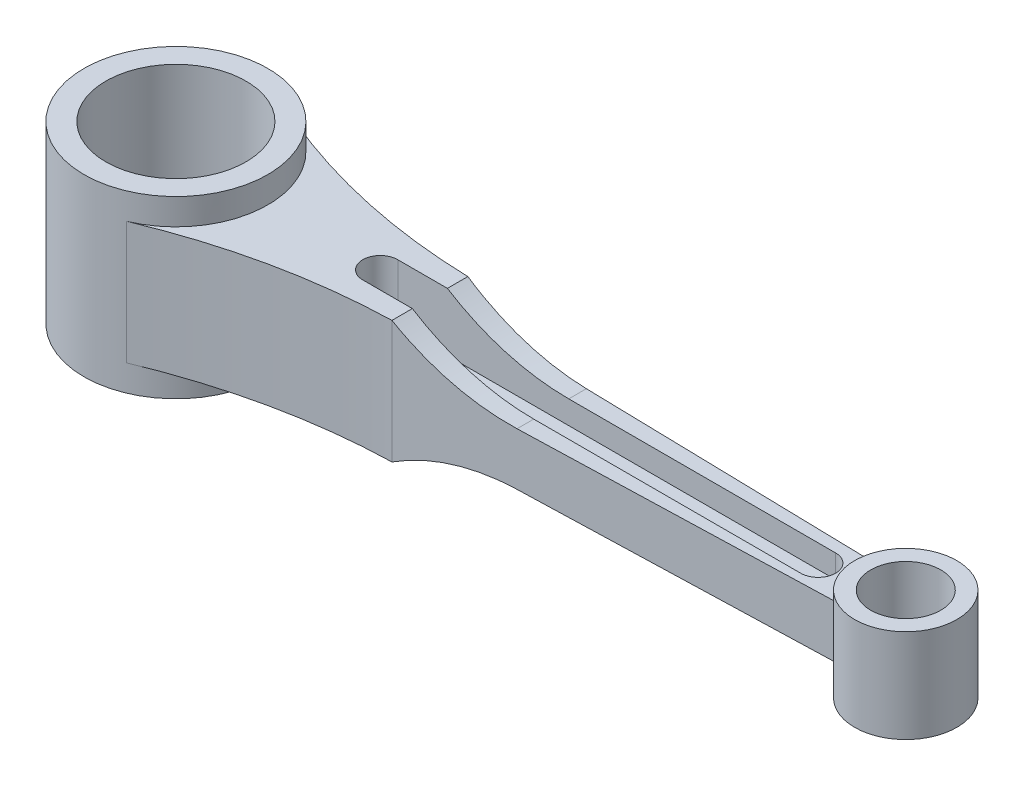
SolidWorks part; units mm, degrees
ref_plane "Front Plane" through (0, 0, 0) normal (0, 0, 1) x (1, 0, 0)
ref_plane "Top Plane" through (0, 0, 0) normal (0, 1, 0) x (1, 0, 0)
ref_plane "Right Plane" through (0, 0, 0) normal (1, 0, 0) x (0, 0, -1)
sketch "Sketch1" plane through (0, 0, 0) normal (0, 1, 0) x (1, 0, 0)
  line L0 (0, 0) -> (150, 0) construction
  line L1 (0, 6) -> (150, 6)
  line L2 (0, -6) -> (150, -6)
  line L3 (17, 13) -> (165.3326, 9.5455)
  line L4 (17, 13) -> (17, -13)
  line L5 (17, -13) -> (164.6777, -8.4545)
  line L6 (17, 13) -> (17, -13) construction
  line L7 (-26.4314, 0) -> (-19.2398, 0) construction
  circle A0 centre (-70, 0) radius 24
  circle A1 centre (-70, 0) radius 31.5
  arc A2 (0, 6) -> (0, -6) centre (0, 0) ccw
  arc A3 (150, -6) -> (150, 6) centre (150, 0) ccw
  circle A4 centre (180, 0) radius 12
  circle A5 centre (180, 0) radius 17.5
  arc A6 (-57.8377, 29.0573) -> (17, 13) centre (22.472, 220.928) ccw
  arc A7 (-57.8377, -29.0573) -> (17, -13) centre (22.472, -220.928) cw
  point P6 (75, 0)
  point P17 (17, 0)
  point P22 (17, 0)
  point P28 (0, 0)
  point P29 (0, 0)
  point P30 (0, 0)
  dimension "D4" = 12
  dimension "D5" = 24
  dimension "D6" = 35
  dimension "D7" = 48
  dimension "D8" = 63
  dimension "D9" = 163
  dimension "D1" = 150
  dimension "D2" = 30
  dimension "D3" = 250
  dimension "D11" = 18
  dimension "D12" = 26
extrude "Boss-Extrude1" add sketch "Sketch1" against normal mid plane 60 contours A1 A0 region at (-44.518, 0, -16.9583)
extrude "Boss-Extrude2" add sketch "Sketch1<4>" against normal mid plane 32 separate body contours A5 A4 region at (184.8376, 0, -16.3024)
sketch "Sketch1<4>" plane through (0, 0, 0) normal (0, 1, 0) x (1, 0, 0) same geometry as "Sketch1"
extrude "Boss-Extrude3" add sketch "Sketch1<6>" along normal mid plane 42 contours A1 A7 L4 L2 A2 L1 A6 region at (-19.1877, 0, 0)
sketch "Sketch1<6>" plane through (0, 0, 0) normal (0, 1, 0) x (1, 0, 0) same geometry as "Sketch1"
extrude "Boss-Extrude4" add sketch "Sketch1<8>" along normal mid plane 18 contours A5 L3 L4 L1 A3 L2 L5 region at (18.5059, 0, -9.5)
sketch "Sketch1<8>" plane through (0, 0, 0) normal (0, 1, 0) x (1, 0, 0) same geometry as "Sketch1"
extrude "Boss-Extrude5" add sketch "Sketch1<9>" along normal mid plane 2.1 contours L2 A3 L1 L4 | L1 A2 L2 L4 region at (6.1025, 0, 0) region at (85.8627, 0, 0)
sketch "Sketch1<9>" plane through (0, 0, 0) normal (0, 1, 0) x (1, 0, 0) same geometry as "Sketch1"
fillet "Fillet1" radius 78 4 edges at (17, -9, 9.5) (17, -9, -9.5) (17, 9, 9.5) (17, 9, -9.5)
